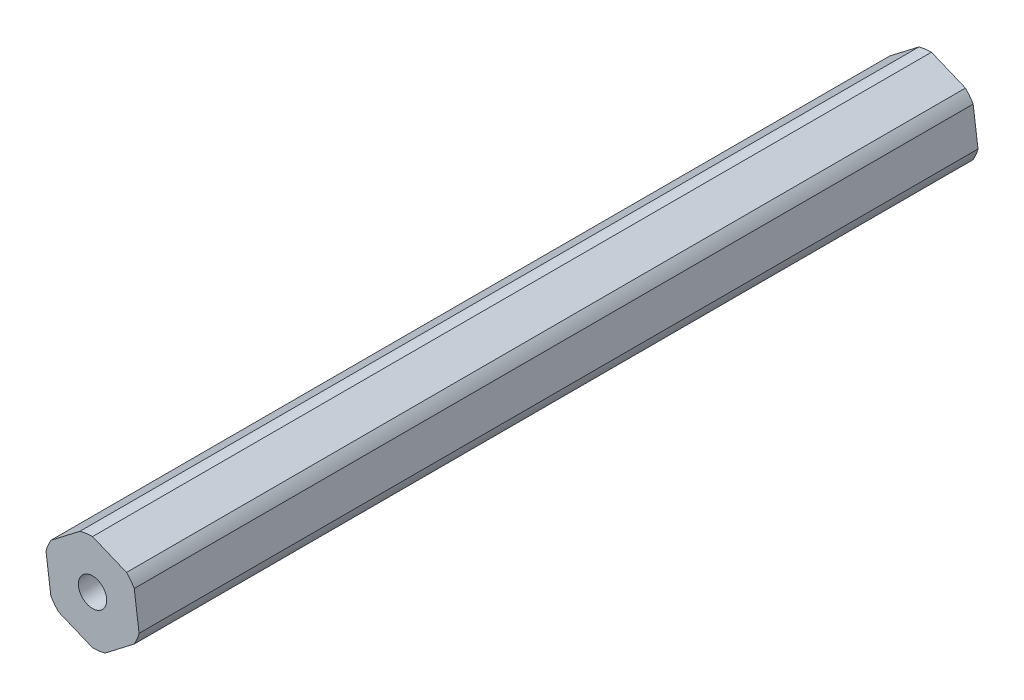
SolidWorks part; units mm, degrees
material "6061-T6 (SS)"
ref_plane "Front Plane" through (0, 0, 0) normal (0, 0, 1) x (1, 0, 0)
ref_plane "Top Plane" through (0, 0, 0) normal (0, 1, 0) x (1, 0, 0)
ref_plane "Right Plane" through (0, 0, 0) normal (1, 0, 0) x (0, 0, -1)
sketch "Sketch1" plane through (0, 0, 0) normal (0, 0, 1) x (1, 0, 0)
  line L1 (-1.7899, 6.6335) -> (-5.9502, 3.4354)
  line L2 (-6.6397, 1.7666) -> (-5.9502, -3.4353)
  line L3 (-4.8498, -4.8668) -> (0, -6.8707)
  line L4 (1.7899, -6.6335) -> (5.9502, -3.4354)
  line L5 (6.6397, -1.7666) -> (5.9502, 3.4353)
  line L6 (4.8498, 4.8668) -> (0, 6.8707)
  circle A0 centre (0, 0) radius 6.35 construction
  arc A1 (-5.9502, 3.4354) -> (-6.6397, 1.7666) centre (0, 0) ccw
  arc A2 (-5.9502, -3.4353) -> (-4.8498, -4.8668) centre (0, 0) ccw
  arc A3 (0, -6.8707) -> (1.7899, -6.6335) centre (0, 0) ccw
  arc A4 (5.9502, -3.4354) -> (6.6397, -1.7666) centre (0, 0) ccw
  arc A5 (5.9502, 3.4353) -> (4.8498, 4.8668) centre (0, 0) ccw
  arc A6 (0, 6.8707) -> (-1.7899, 6.6335) centre (0, 0) ccw
  dimension "D1" = 12.7
  dimension "D2" = 13.7414
extrude "Boss-Extrude1" add sketch "Sketch1" along normal blind 119.6975 contours L1 A1 L2 A2 L3 A3 L4 A4 L5 A5 L6 A6
sketch "Sketch8" plane through (0, 0, 0) normal (0, 0, -1) x (-1, 0, 0)
  point P0 (0, 0)
hole_wizard "1/4-20 Tapped Hole2" positions "Sketch11" profile "Sketch12" tap size "1/4-20" standard "ANSI Inch"
sketch "Sketch11" plane through (0, 0, 0) normal (0, 0, -1) x (-1, 0, 0)
  point P0 (0, 0)
cosmetic thread "Hole Thread5" parameters "D1"=12.7, "D2"=6.35
sketch "Sketch12" plane through (0, 0, 0) normal (1, 0, 0) x (0, 1, 0)
  line L0 (0, 0) -> (0, 18.0438)
  line L1 (0, 18.0438) -> (2.5527, 16.51)
  line L2 (2.5527, 16.51) -> (2.5527, 0)
  line L5 (2.5527, 0) -> (0, 0)
  line L10 (0, 18.0438) -> (-2.5527, 16.51) construction
  line L11 (0, -6.35) -> (0, 107.95) construction
  dimension "Tap Drill Dia." = 5.1054
  dimension "Tap Drill Depth" = 16.51
  dimension "Drill Angle" = 118
sketch "Sketch14" plane through (0, 0, 119.6975) normal (0, 0, 1) x (1, 0, 0)
  line L0 (4.8498, 4.8668) -> (0, 6.8707) construction
  line L7 (-1.7899, 6.6335) -> (-5.9502, 3.4354)
  line L8 (-6.6397, 1.7666) -> (-5.9502, -3.4353)
  line L9 (-4.8498, -4.8668) -> (0, -6.8707)
  line L10 (1.7899, -6.6335) -> (5.9502, -3.4354)
  line L11 (6.6397, -1.7666) -> (5.9502, 3.4353)
  line L12 (4.8498, 4.8668) -> (0, 6.8707)
  line L13 (-1.7899, 6.6335) -> (-5.9502, 3.4354)
  line L14 (-6.6397, 1.7666) -> (-5.9502, -3.4353)
  line L15 (-4.8498, -4.8668) -> (0, -6.8707)
  line L16 (1.7899, -6.6335) -> (5.9502, -3.4354)
  line L17 (6.6397, -1.7666) -> (5.9502, 3.4353)
  line L18 (4.8498, 4.8668) -> (0, 6.8707)
  circle A0 centre (0, 0) radius 6.35
  arc A7 (0, 6.8707) -> (-1.7899, 6.6335) centre (0, 0) ccw
  arc A8 (-5.9502, 3.4354) -> (-6.6397, 1.7666) centre (0, 0) ccw
  arc A9 (-5.9502, -3.4353) -> (-4.8498, -4.8668) centre (0, 0) ccw
  arc A10 (0, -6.8707) -> (1.7899, -6.6335) centre (0, 0) ccw
  arc A11 (5.9502, -3.4354) -> (6.6397, -1.7666) centre (0, 0) ccw
  arc A12 (5.9502, 3.4353) -> (4.8498, 4.8668) centre (0, 0) ccw
  arc A13 (0, 6.8707) -> (-1.7899, 6.6335) centre (0, 0) ccw
  arc A14 (-5.9502, 3.4354) -> (-6.6397, 1.7666) centre (0, 0) ccw
  arc A15 (-5.9502, -3.4353) -> (-4.8498, -4.8668) centre (0, 0) ccw
  arc A16 (0, -6.8707) -> (1.7899, -6.6335) centre (0, 0) ccw
  arc A17 (5.9502, -3.4354) -> (6.6397, -1.7666) centre (0, 0) ccw
  arc A18 (5.9502, 3.4353) -> (4.8498, 4.8668) centre (0, 0) ccw
  dimension "D1" = 0
hole_wizard "#10-32 Tapped Hole1" positions "Sketch15" profile "Sketch16" tap size "#10-32" standard "ANSI Inch"
sketch "Sketch15" plane through (0, 0, 119.6975) normal (0, 0, 1) x (1, 0, 0)
  point P0 (0, 0)
sketch "Sketch16" plane through (0, 0, 119.6975) normal (1, 0, 0) x (0, -1, 0)
  line L0 (0, 0) -> (0, 14.8277)
  line L1 (0, 14.8277) -> (2.0193, 13.6144)
  line L2 (2.0193, 13.6144) -> (2.0193, 0)
  line L5 (2.0193, 0) -> (0, 0)
  line L10 (0, 14.8277) -> (-2.0193, 13.6144) construction
  line L11 (0, -6.35) -> (0, 107.95) construction
  dimension "Tap Drill Dia." = 4.0386
  dimension "Tap Drill Depth" = 13.6144
  dimension "Drill Angle" = 118
cosmetic thread "Hole Thread6" parameters "D1"=9.652, "D2"=4.826
